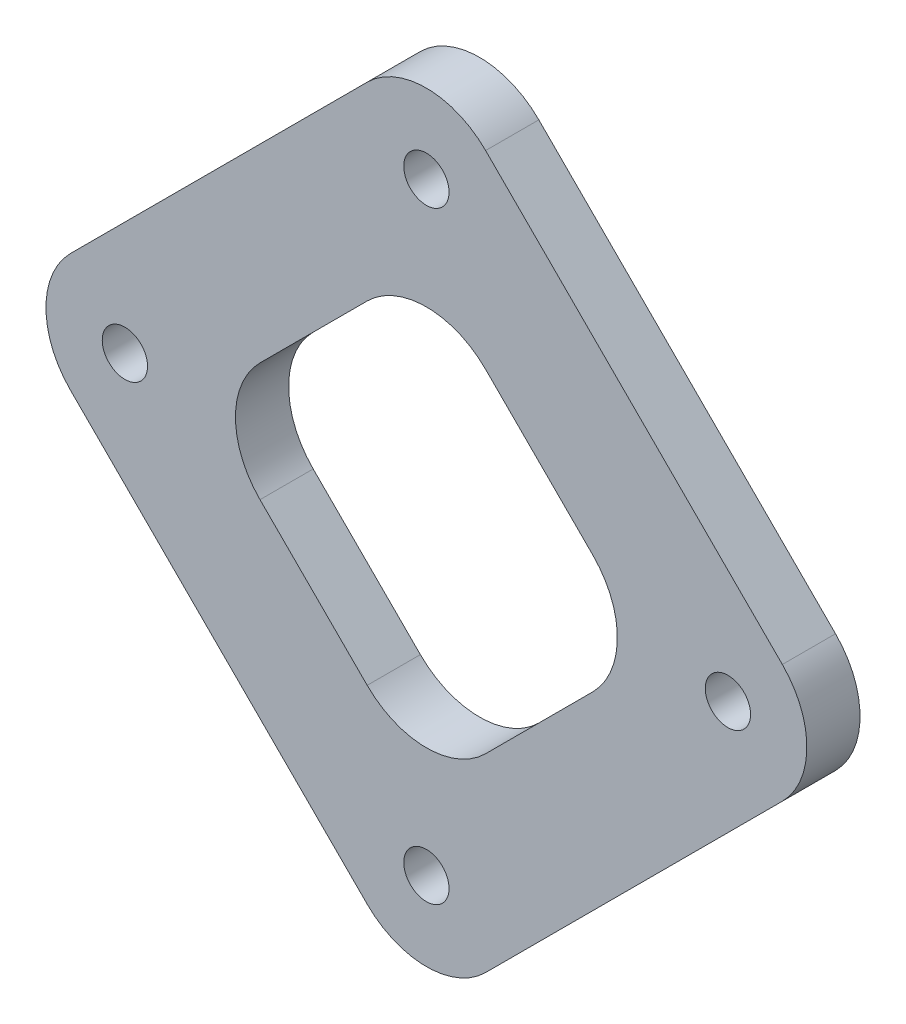
SolidWorks part; units mm, degrees
material "6061-T6 (SS)"
ref_plane "Front" through (0, 0, 0) normal (0, 0, 1) x (1, 0, 0)
ref_plane "Top" through (0, 0, 0) normal (0, 1, 0) x (1, 0, 0)
ref_plane "Right" through (0, 0, 0) normal (1, 0, 0) x (0, 0, -1)
ref_axis "side-side" through (80.9, 0, 0) along (-1, 0, 0)
ref_axis "up-down" through (0, 50, 0) along (0, -1, 0)
ref_axis "front-back" through (0, 0, -80.9) along (0, 0, 1)
sketch "Sketch2" plane through (0, 0, 0) normal (0, 0, 1) x (1, 0, 0)
  line L0 (0, 13.4704) -> (13.4704, 0)
  line L1 (0, 13.4704) -> (-13.4704, 0)
  line L2 (13.4704, 0) -> (0, -13.4704)
  line L3 (-13.4704, 0) -> (0, -13.4704)
  line L4 (0, -50) -> (0, 50) construction
  line L5 (50, 0) -> (-50, 0) construction
  line L6 (0, 24.7841) -> (24.7841, 0)
  line L7 (24.7841, 0) -> (0, -24.7841)
  line L8 (-24.7841, 0) -> (0, -24.7841)
  line L9 (0, 24.7841) -> (-24.7841, 0)
  circle A0 centre (0, 18) radius 1.8542 construction
  circle A1 centre (-18, 0) radius 1.8542 construction
  circle A2 centre (0, -18) radius 1.8542 construction
  circle A3 centre (18, 0) radius 1.8542 construction
  circle A4 centre (0, 0) radius 18 construction
  point P23 (0, 0)
  dimension "D3" = 3.7084
  dimension "D4" = 36
  dimension "D1" = 19.05
  dimension "D2" = 8
extrude "Boss-Extrude1" add sketch "Sketch2" along normal blind 3.175
fillet "Fillet1" radius 5 4 edges at (-13.4704, 0, 1.5875) (0, -13.4704, 1.5875) (13.4704, 0, 1.5875) (0, 13.4704, 1.5875)
hole_wizard "#6-32 Tapped Hole1" positions "Sketch3" profile "Sketch4" tap size "#6-32" standard "ANSI Inch"
sketch "Sketch3" plane through (0, 0, 0) normal (0, 0, -1) x (-1, 0, 0)
  point P0 (-18, 0)
  point P2 (0, 18)
  point P8 (0, -18)
  point P11 (18, 0)
sketch "Sketch4" plane through (18, 0, 0) normal (1, 0, 0) x (0, 1, 0)
  line L0 (0, 0) -> (0, 11.7857)
  line L1 (0, 11.7857) -> (1.3525, 10.973)
  line L2 (1.3525, 10.973) -> (1.3525, 0)
  line L5 (1.3525, 0) -> (0, 0)
  line L10 (0, 11.7857) -> (-1.3525, 10.973) construction
  line L11 (0, -6.35) -> (0, 107.95) construction
  dimension "Tap Drill Dia." = 2.7051
  dimension "Tap Drill Depth" = 10.973
  dimension "Drill Angle" = 118
fillet "Fillet2" radius 5 4 edges at (24.7841, 0, 1.5875) (0, -24.7841, 1.5875) (-24.7841, 0, 1.5875) (0, 24.7841, 1.5875)
